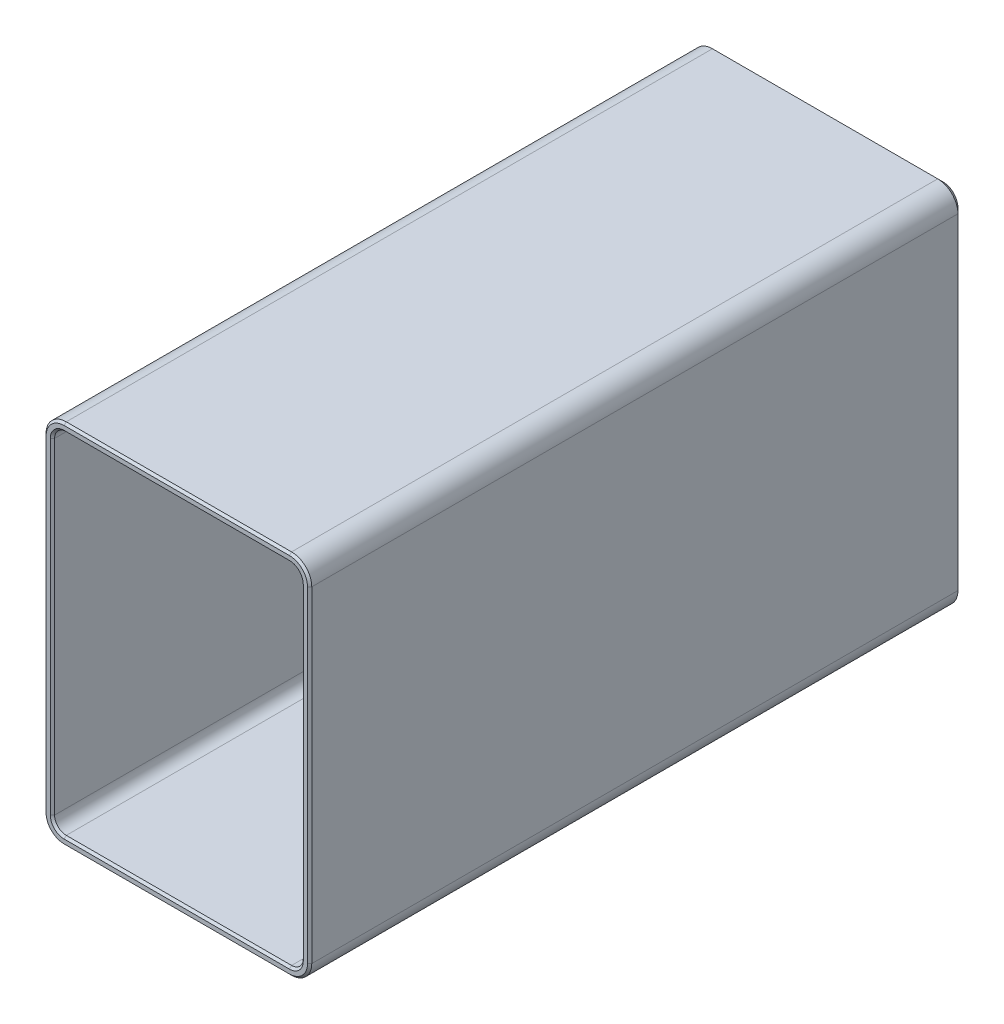
SolidWorks part; units mm, degrees
ref_plane "Front" through (0, 0, 0) normal (0, 0, 1) x (1, 0, 0)
ref_plane "Top" through (0, 0, 0) normal (0, 1, 0) x (1, 0, 0)
ref_plane "Right" through (0, 0, 0) normal (1, 0, 0) x (0, 0, -1)
sketch "Sketch1" plane through (0, 0, 0) normal (0, 0, 1) x (1, 0, 0)
  line L1 (-21.2, -34.5) -> (21.2, -34.5)
  line L2 (-25, -30.7) -> (-25, 30.7)
  line L3 (-21.2, 34.5) -> (21.2, 34.5)
  line L4 (25, -30.7) -> (25, 30.7)
  line L5 (-25, -34.5) -> (25, 34.5) construction
  line L6 (-25, 34.5) -> (25, -34.5) construction
  arc A0 (21.2, 34.5) -> (25, 30.7) centre (21.2, 30.7) cw
  arc A1 (21.2, -34.5) -> (25, -30.7) centre (21.2, -30.7) ccw
  arc A2 (-21.2, -34.5) -> (-25, -30.7) centre (-21.2, -30.7) cw
  arc A3 (-25, 30.7) -> (-21.2, 34.5) centre (-21.2, 30.7) cw
  point P0 (0, 0)
  dimension "D3" = 3.8
  dimension "D1" = 50
  dimension "D2" = 69
extrude "Walls" add sketch "Sketch1" along normal blind 123 thin thin type one direction reverse wall 1.6
sketch "Sketch2" plane through (0, 0, 0) normal (0, 0, -1) x (-1, 0, 0)
  line L4 (-25, 30.7) -> (-25, -30.7)
  line L5 (-21.2, -34.5) -> (21.2, -34.5)
  line L6 (25, -30.7) -> (25, 30.7)
  line L7 (21.2, 34.5) -> (-21.2, 34.5)
  line L8 (-25, 30.7) -> (-25, -30.7)
  line L9 (-21.2, -34.5) -> (21.2, -34.5)
  line L10 (25, -30.7) -> (25, 30.7)
  line L11 (21.2, 34.5) -> (-21.2, 34.5)
  arc A4 (-21.2, 34.5) -> (-25, 30.7) centre (-21.2, 30.7) ccw
  arc A5 (-25, -30.7) -> (-21.2, -34.5) centre (-21.2, -30.7) ccw
  arc A6 (21.2, -34.5) -> (25, -30.7) centre (21.2, -30.7) ccw
  arc A7 (25, 30.7) -> (21.2, 34.5) centre (21.2, 30.7) ccw
  arc A8 (-21.2, 34.5) -> (-25, 30.7) centre (-21.2, 30.7) ccw
  arc A9 (-25, -30.7) -> (-21.2, -34.5) centre (-21.2, -30.7) ccw
  arc A10 (21.2, -34.5) -> (25, -30.7) centre (21.2, -30.7) ccw
  arc A11 (25, 30.7) -> (21.2, 34.5) centre (21.2, 30.7) ccw
  dimension "D1" = 0
extrude "Floor" add sketch "Sketch2" against normal blind 2.6
chamfer "Bottom Chamfers" distance 1 angle 45 8 edges at (0, 34.5, 0) (-23.887, 33.387, 0) (-25, 0, 0) (-23.887, -33.387, 0) (0, -34.5, 0) (23.887, -33.387, 0) (25, 0, 0) (23.887, 33.387, 0)
chamfer "Top Chamfers" distance 0.4 angle 45 16 edges at (-22.7556, 32.2556, 123) (-23.4, 0, 123) (-22.7556, -32.2556, 123) (0, -32.9, 123) (22.7556, -32.2556, 123) (23.4, 0, 123) (22.7556, 32.2556, 123) (0, 32.9, 123) (25, 0, 123) (23.887, -33.387, 123) (0, -34.5, 123) (-23.887, -33.387, 123) (-25, 0, 123) (-23.887, 33.387, 123) (0, 34.5, 123) (23.887, 33.387, 123)
fillet "Inside Bottom Fillet" radius 1 8 edges at (23.4, 0, 2.6) (22.7556, -32.2556, 2.6) (0, -32.9, 2.6) (-22.7556, -32.2556, 2.6) (-23.4, 0, 2.6) (-22.7556, 32.2556, 2.6) (0, 32.9, 2.6) (22.7556, 32.2556, 2.6)
equation "\"Width\" = 50mm"
equation "\"Length\" = 69mm"
equation "\"Depth\" = 123mm"
equation "\"D1@Sketch1\"=\"Width\""
equation "\"D2@Sketch1\"=\"Length\""
equation "\"D1@Walls\"=\"Depth\""
